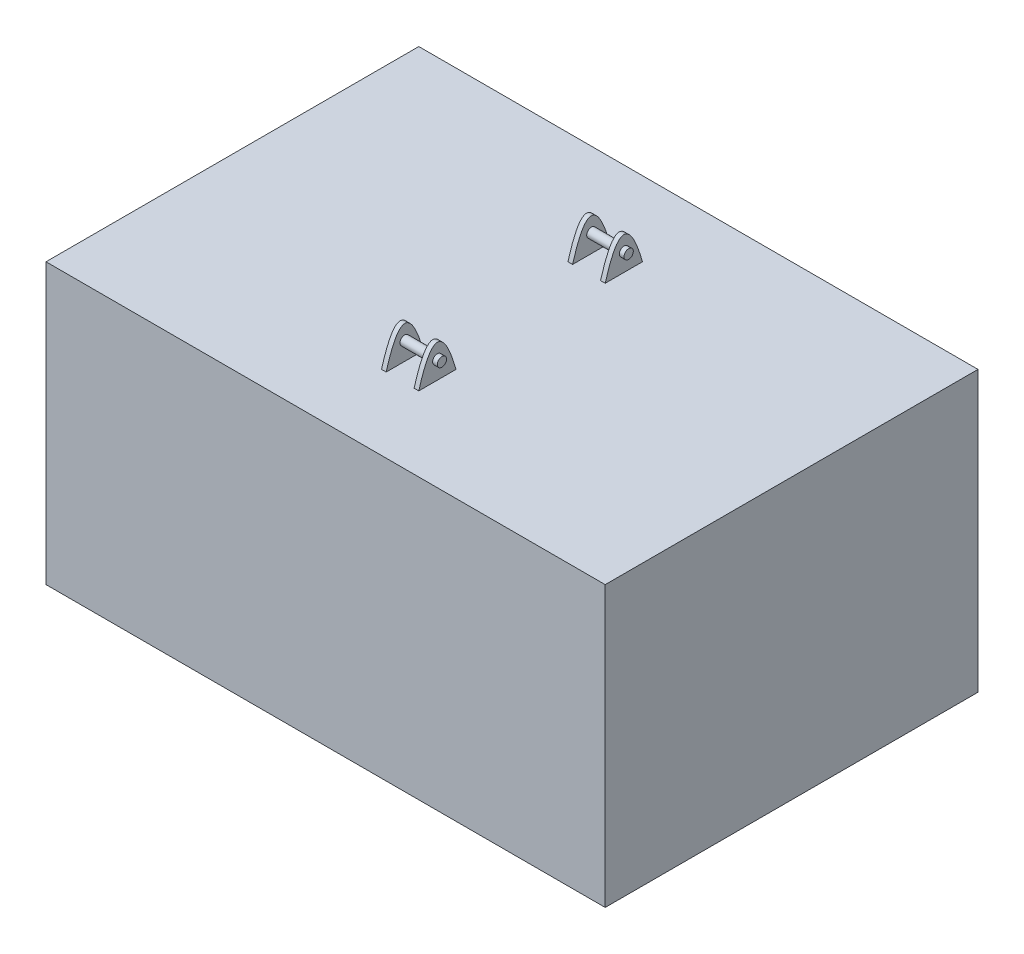
SolidWorks part; units mm, degrees
material "AISI 304"
ref_plane "Front Plane" through (0, 0, 0) normal (0, 0, 1) x (1, 0, 0)
ref_plane "Top Plane" through (0, 0, 0) normal (0, 1, 0) x (1, 0, 0)
ref_plane "Right Plane" through (0, 0, 0) normal (1, 0, 0) x (0, 0, -1)
sketch "Sketch2" plane through (0, 0, 0) normal (1, 0, 0) x (0, 0, -1)
  line L1 (-200, 150) -> (200, 150)
  line L2 (-200, 150) -> (-200, -150)
  line L3 (-200, -150) -> (200, -150)
  line L4 (200, 150) -> (200, -150)
  line L5 (-200, 150) -> (200, -150) construction
  line L6 (-200, -150) -> (200, 150) construction
  point P0 (0, 0)
extrude "Boss-Extrude1" add sketch "Sketch2" along normal blind 300 and the other way blind 300
sketch "Sketch4" plane through (0, 150, 0) normal (0, 1, 0) x (1, 0, 0)
  point P0 (0, -100)
  point P1 (0, 100)
ref_plane "Plane1" through (20, 0, 0) normal (1, 0, 0) x (0, 0, -1)
sketch "Sketch9" plane through (20, 0, 0) normal (1, 0, 0) x (0, 0, -1)
  line L0 (-80, 150) -> (-100, 150)
  line L1 (200, 150) -> (-200, 150) construction
  line L2 (-100, 150) -> (-120, 150)
  spline S0 degree 2 poles (-120, 150) (-100, 220.3696) (-80, 150) knots 0 0 0 1 1 1
extrude "Boss-Extrude4" add sketch "Sketch9" against normal blind 5
sketch "Sketch10" plane through (20, 0, 0) normal (1, 0, 0) x (0, 0, -1)
  circle A0 centre (-100.1679, 169.5884) radius 5
extrude "Boss-Extrude5" add sketch "Sketch10" along normal blind 5 and the other way blind 20
mirror "Mirror1" about plane through (0, 0, 0) normal (1, 0, 0) of "Boss-Extrude5", "Boss-Extrude4"
mirror "Mirror2" about plane through (0, 0, 0) normal (0, 0, 1) of "Mirror1", "Boss-Extrude5", "Boss-Extrude4"
